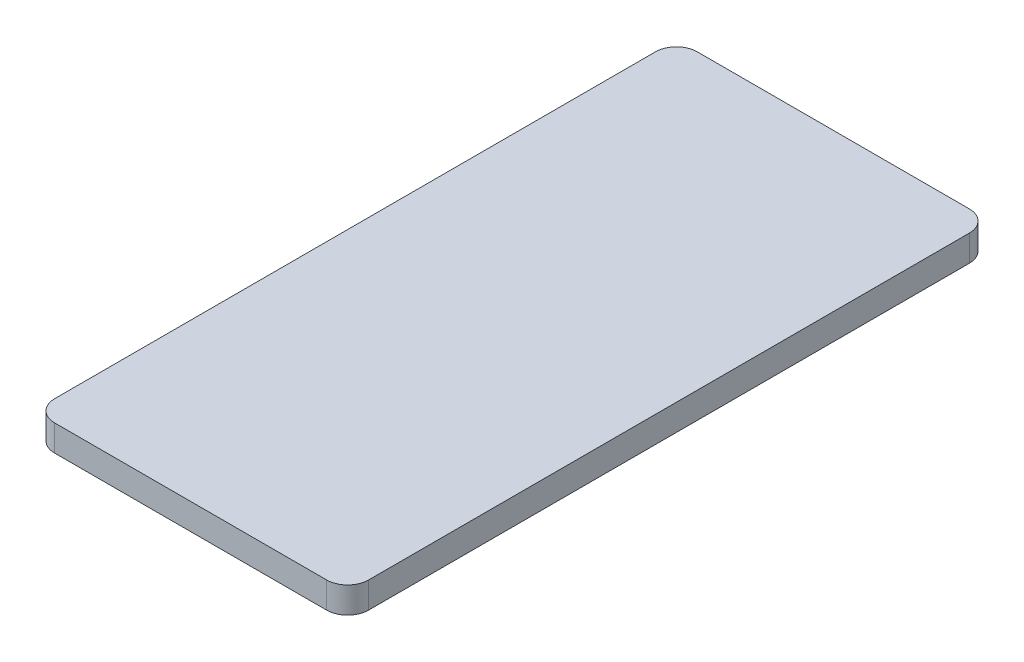
SolidWorks part; units mm, degrees
material "Acrylic (Medium-high impact)"
ref_plane "Front Plane" through (0, 0, 0) normal (0, 0, 1) x (1, 0, 0)
ref_plane "Top Plane" through (0, 0, 0) normal (0, 1, 0) x (1, 0, 0)
ref_plane "Right Plane" through (0, 0, 0) normal (1, 0, 0) x (0, 0, -1)
ref_plane "Plane1" through (0, 0, 0) normal (0, 1, 0) x (1, 0, 0)
sketch "Sketch1" plane through (0, 0, 0) normal (0, 1, 0) x (1, 0, 0)
  line L1 (0, 0) -> (38.1, 0)
  line L2 (0, 0) -> (0, 78)
  line L3 (0, 78) -> (38.1, 78)
  line L4 (38.1, 0) -> (38.1, 78)
  dimension "D1" = 38.1
  dimension "D2" = 78
extrude "Boss-Extrude1" add sketch "Sketch1" along normal blind 3.175
fillet "Fillet1" radius 2.54 4 edges at (38.1, 1.5875, 0) (0, 1.5875, 0) (38.1, 1.5875, -78) (0, 1.5875, -78)
